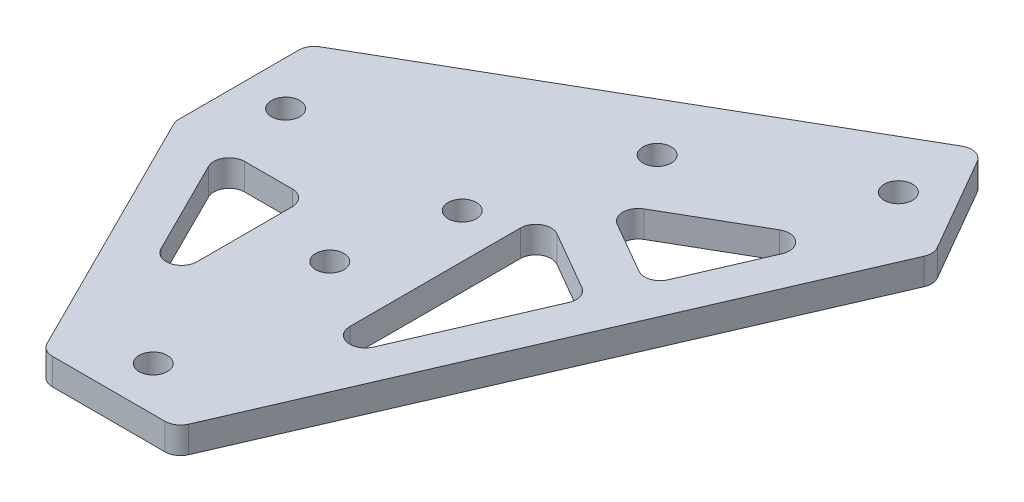
SolidWorks part; units mm, degrees
ref_plane "正面" through (0, 0, 0) normal (0, 0, 1) x (1, 0, 0)
ref_plane "平面" through (0, 0, 0) normal (0, 1, 0) x (1, 0, 0)
ref_plane "右側面" through (0, 0, 0) normal (1, 0, 0) x (0, 0, -1)
sketch "ｽｹｯﾁ2" plane through (0, 0.3953, 0) normal (0, 1, 0) x (1, 0, 0)
  line L0 (275.032, 154.7676) -> (267.532, 167.7579) construction
  line L1 (267.532, 167.7579) -> (163.6089, 107.7579) construction
  line L2 (163.6089, 107.7579) -> (171.1089, 94.7676) construction
  line L3 (171.1089, 94.7676) -> (275.032, 154.7676) construction
  line L4 (171.1089, 79.7676) -> (156.1089, 79.7676) construction
  line L5 (156.1089, 79.7676) -> (156.1089, -61.2324) construction
  line L6 (156.1089, -61.2324) -> (171.1089, -61.2324) construction
  line L7 (171.1089, -61.2324) -> (171.1089, 79.7676) construction
  line L8 (171.1089, 79.7676) -> (171.1089, 94.7676) construction
  line L9 (171.1089, 94.7676) -> (-48.8911, 94.7676) construction
  line L10 (-48.8911, 94.7676) -> (-48.8911, 79.7676) construction
  line L11 (-48.8911, 79.7676) -> (171.1089, 79.7676) construction
  line L12 (275.032, 154.7676) -> (267.532, 167.7579) construction
  line L13 (267.532, 167.7579) -> (163.6089, 107.7579) construction
  line L14 (163.6089, 107.7579) -> (171.1089, 94.7676) construction
  line L15 (171.1089, 94.7676) -> (275.032, 154.7676) construction
  line L16 (171.1089, 79.7676) -> (156.1089, 79.7676) construction
  line L17 (156.1089, 79.7676) -> (156.1089, -61.2324) construction
  line L18 (156.1089, -61.2324) -> (171.1089, -61.2324) construction
  line L19 (171.1089, -61.2324) -> (171.1089, 79.7676) construction
  line L20 (171.1089, 79.7676) -> (171.1089, 94.7676) construction
  line L21 (171.1089, 94.7676) -> (-48.8911, 94.7676) construction
  line L22 (-48.8911, 94.7676) -> (-48.8911, 79.7676) construction
  line L23 (-48.8911, 79.7676) -> (171.1089, 79.7676) construction
  line L24 (0, 15) -> (103.923, 75) construction
  line L25 (0, 0) -> (-220, 0) construction
  line L26 (0, 0) -> (0, 15) construction
  line L27 (0, 15) -> (-220, 15) construction
  line L28 (-220, 0) -> (-220, 15) construction
  line L29 (0, 0) -> (-15, 0) construction
  line L30 (0, 0) -> (0, -141) construction
  line L31 (0, -141) -> (-15, -141) construction
  line L32 (-15, 0) -> (-15, -141) construction
  line L33 (103.923, 75) -> (96.423, 87.9904) construction
  line L34 (96.423, 87.9904) -> (-7.5, 27.9904) construction
  line L35 (-7.5, 27.9904) -> (0, 15) construction
  dimension "D1" = 15
  dimension "D2" = 220
  dimension "D3" = 141
  dimension "D4" = 15
  dimension "D5" = 120
  dimension "D6" = 15
  dimension "D7" = 120
sketch "ｽｹｯﾁ4" plane through (0, 0, 0) normal (0, 1, 0) x (1, 0, 0)
  line L0 (103.923, 75) -> (96.423, 87.9904) construction
  line L1 (0, 15) -> (103.923, 75) construction
  line L2 (96.423, 87.9904) -> (-7.5, 27.9904) construction
  line L3 (-7.5, 27.9904) -> (0, 15) construction
  line L4 (0, -141) -> (-15, -141) construction
  line L5 (0, 0) -> (0, -141) construction
  line L6 (-15, 0) -> (-15, -141) construction
  line L7 (0, 0) -> (0, 15) construction
  line L8 (-220, 0) -> (-220, 15) construction
  line L9 (0, 0) -> (-220, 0) construction
  line L10 (0, 15) -> (-220, 15) construction
  line L11 (103.923, 75) -> (96.423, 87.9904) construction
  line L12 (0, 15) -> (103.923, 75) construction
  line L13 (96.423, 87.9904) -> (-7.5, 27.9904) construction
  line L14 (-7.5, 27.9904) -> (0, 15) construction
  line L15 (0, -141) -> (-15, -141) construction
  line L16 (0, 0) -> (0, -141) construction
  line L17 (-15, 0) -> (-15, -141) construction
  line L18 (0, 0) -> (0, 15) construction
  line L19 (-220, 0) -> (-220, 15) construction
  line L20 (0, 0) -> (-220, 0) construction
  line L21 (0, 15) -> (-220, 15) construction
  line L22 (-3.75, 21.4952) -> (17.9006, 33.9952) construction
  line L23 (0, 7.5) -> (-25, 7.5) construction
  line L24 (-7.5, 0) -> (-7.5, -25) construction
  line L25 (-30, 0) -> (-30, 15)
  line L26 (-30, 15) -> (18.4808, 42.9904)
  line L27 (18.4808, 42.9904) -> (25.9808, 30)
  line L28 (25.9808, 30) -> (0, -30)
  line L29 (0, -30) -> (-15, -30)
  line L30 (-15, -30) -> (-30, 0)
  circle A0 centre (0.5801, 23.9952) radius 1.6
  circle A1 centre (-5, 7.5) radius 1.6
  circle A2 centre (-7.5, -5) radius 1.6
  circle A3 centre (-7.5, -25) radius 1.6
  circle A4 centre (-25, 7.5) radius 1.6
  circle A5 centre (17.9006, 33.9952) radius 1.6
  dimension "D4" = 3.2
  dimension "D5" = 3.2
  dimension "D6" = 3.2
  dimension "D7" = 3.2
  dimension "D8" = 3.2
  dimension "D9" = 3.2
  dimension "D1" = 25
  dimension "D2" = 25
  dimension "D3" = 25
  dimension "D10" = 20
  dimension "D11" = 20
  dimension "D12" = 20
  dimension "D13" = 5
  dimension "D14" = 5
  dimension "D15" = 5
extrude "ﾎﾞｽ - 押し出し1" add sketch "ｽｹｯﾁ4" along normal mid plane 3
sketch "ｽｹｯﾁ5" plane through (0, 1.5, 0) normal (0, 1, 0) x (1, 0, 0)
  line L0 (-7.5, 27.9904) -> (0, 15) construction
  line L1 (0, 15) -> (103.923, 75) construction
  line L2 (0, 0) -> (0, 15) construction
  line L3 (0, 15) -> (-220, 15) construction
  line L4 (0, 0) -> (-220, 0) construction
  line L5 (-15, 0) -> (-15, -141) construction
  line L6 (-30, 0) -> (-15, -30)
  line L7 (-15, -30) -> (0, -30)
  line L8 (0, -30) -> (25.9808, 30)
  line L9 (25.9808, 30) -> (18.4808, 42.9904)
  line L10 (18.4808, 42.9904) -> (-30, 15)
  line L11 (-30, 15) -> (-30, 0)
  line L12 (-30, 0) -> (-15, -30)
  line L13 (-15, -30) -> (0, -30)
  line L14 (0, -30) -> (25.9808, 30)
  line L15 (25.9808, 30) -> (18.4808, 42.9904)
  line L16 (18.4808, 42.9904) -> (-30, 15)
  line L17 (-30, 15) -> (-30, 0)
  line L18 (0, 0) -> (0, -141) construction
  line L19 (-7.5, 27.9904) -> (0, 15)
  line L20 (0, 15) -> (103.923, 75)
  line L21 (0, 0) -> (0, 15)
  line L22 (0, 15) -> (-220, 15)
  line L23 (0, 0) -> (-220, 0)
  line L24 (-15, 0) -> (-15, -141)
  line L25 (0, 0) -> (0, -141)
  line L26 (-2.9552, -25.5) -> (20.9517, 29.7106)
  line L27 (20.9517, 29.7106) -> (16.8336, 36.8433)
  line L28 (16.8336, 36.8433) -> (-25.5, 12.4019)
  line L29 (-25.5, 12.4019) -> (-25.5, 1.0623)
  line L30 (-25.5, 1.0623) -> (-12.2188, -25.5)
  line L31 (-12.2188, -25.5) -> (-2.9552, -25.5)
  line L32 (0, 15) -> (11.6654, 8.265) construction
  line L33 (0, 15) -> (-10.5, 21.0622) construction
  line L34 (-13, 19.6188) -> (10.6654, 5.9555)
  line L37 (-21, 15) -> (-5.25, 24.0933) construction
  line L38 (12.6654, 10.5744) -> (-8, 22.5056)
  line L40 (0, 15) -> (3.4641, 13)
  line L41 (0, 15) -> (-3.4641, 17)
  line L42 (-4.6188, 15) -> (-2.3094, 19)
  line L43 (0, 7) -> (6.9282, 19)
  line L44 (1.25, 17.1651) -> (-9.25, 23.2272) construction
  line L47 (-1.25, 12.8349) -> (10.4154, 6.0999) construction
  circle A1 centre (0.5801, 23.9952) radius 1.6
  circle A2 centre (0.5801, 23.9952) radius 1.6
  circle A3 centre (-5, 7.5) radius 1.6
  circle A4 centre (-5, 7.5) radius 1.6
  circle A5 centre (-7.5, -5) radius 1.6
  circle A6 centre (-7.5, -5) radius 1.6
  circle A7 centre (-7.5, -25) radius 1.6
  circle A8 centre (-7.5, -25) radius 1.6
  circle A9 centre (-25, 7.5) radius 1.6
  circle A10 centre (-25, 7.5) radius 1.6
  circle A11 centre (17.9006, 33.9952) radius 1.6
  circle A12 centre (17.9006, 33.9952) radius 1.6
  point P58 (-3.4641, 17)
  point P61 (3.4641, 13)
  dimension "D9" = 2.5
  dimension "D12" = 60
  dimension "D13" = 4
  dimension "D14" = 4
  dimension "D1" = 0
  dimension "D2" = 0
  dimension "D3" = 0
  dimension "D4" = 0
  dimension "D5" = 0
  dimension "D6" = 0
  dimension "D7" = 0
  dimension "D8" = 4.5
extrude "ｶｯﾄ - 押し出し2" cut sketch "ｽｹｯﾁ5" against normal blind 3 contours L43 L38 L26 L20 | L38 L43 L20 | L21 L43 L34 | L43 L21 L25 L26 L34 | L23 L30 L24 region at (-18.3229, 1.5, 6.6459) region at (3.6557, 1.5, 0.5658) region at (11.9477, 1.5, -17.8006) region at (0.738, 1.5, -9.9827) region at (4.7141, 1.5, -16.8695)
fillet "ﾌｨﾚｯﾄ2" radius 1.75 15 edges at (-15, 0, 19.9377) (0, 0, 18.6752) (10.6654, 0, -5.9555) (12.6654, 0, -10.5744) (2.5, 0, -16.4434) (19.4424, 0, -26.2251) (-24.9688, 0, 0) (-15, 0, 30) (0, 0, 30) (25.9808, 0, -30) (18.4808, 0, -42.9904) (-30, 0, -15) (-30, 0, 0) (0, 0, -12.1132) (-15, 0, 0)
